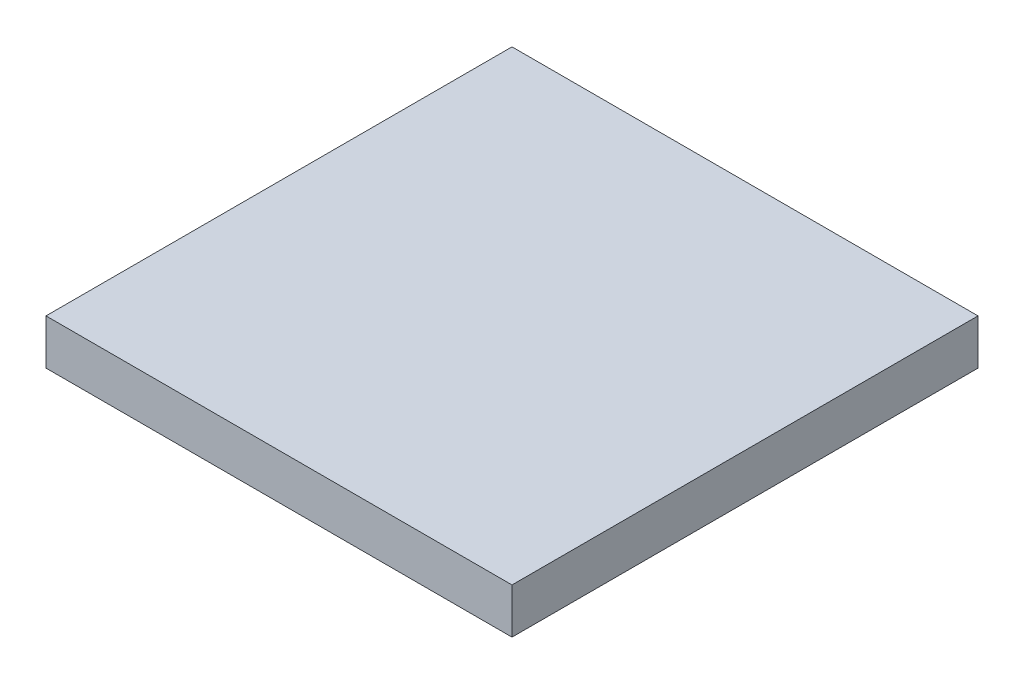
SolidWorks part; units mm, degrees
ref_plane "Front Plane" through (0, 0, 0) normal (0, 0, 1) x (1, 0, 0)
ref_plane "Top Plane" through (0, 0, 0) normal (0, 1, 0) x (1, 0, 0)
ref_plane "Right Plane" through (0, 0, 0) normal (1, 0, 0) x (0, 0, -1)
sketch "Sketch1" plane through (0, 0, 0) normal (0, 1, 0) x (1, 0, 0)
  line L1 (-5.15, -5.15) -> (5.15, -5.15)
  line L2 (-5.15, -5.15) -> (-5.15, 5.15)
  line L3 (-5.15, 5.15) -> (5.15, 5.15)
  line L4 (5.15, -5.15) -> (5.15, 5.15)
  line L5 (-5.15, -5.15) -> (5.15, 5.15) construction
  line L6 (-5.15, 5.15) -> (5.15, -5.15) construction
  point P0 (0, 0)
  dimension "D1" = 10.3
  dimension "D2" = 10.3
extrude "chip_lid" add sketch "Sketch1" along normal blind 1
equation "\"pcb_length\"= 40 ' length of the chip in the direction of the feadline"
equation "\"pcb_side\"= 20    ' length of the chip in the other direction"
equation "\"pcb_width\"= 1"
equation "\"wall_width\"= 1  ' minimal width from the box walls"
equation "\"route_width\"= 1 ' The width of the trace on the lid for not touching the signal roates."
equation "\"route_clearence\"= 0.4 ' The clearence depth of the trace on the lid for not touching the signal roates."
equation "\"route_chip_clearence\"= 1"
equation "\"port_count\"= 2"
equation "\"port_space\"= 1.5"
equation "\"port_length\"= 5.1"
equation "\"port_width\"= 5.1"
equation "\"chip_length\"= 6.3 ' length of the chip in the direction of the feadline"
equation "\"chip_side\"= 6.3 ' length of the chip in the other direction"
equation "\"pedestal_depth\"= 1 ' depth of the pedestal under the chip"
equation "\"chip_leg\"= 0.8  ' size of the legs the chip lay on in case there is pedestal"
equation "\"wing_length\"= 10 ' Mounting wing size"
equation "\"wing_width\"= 1 ' mounting wing width"
equation "\"bonding_clearence\"= 1"
equation "\"box_height\"= \"wall_width\" + \"pedestal_depth\" + \"pcb_width\""
equation "\"box_length\"= \"pcb_length\" + 2 * \"wall_width\""
equation "\"box_side\"= \"pcb_side\" + 2 * \"wall_width\""
equation "\"D1@Sketch1\"=\"chip_length\"+2*\"wall_width\"+2*\"bonding_clearence\""
equation "\"D1@chip_lid\" = \"wall_width\""
equation "\"D2@Sketch1\"=\"chip_side\"+2*\"wall_width\"+2*\"bonding_clearence\""
equation "\"chip_width\"= 0.4 ' width of the chip"
